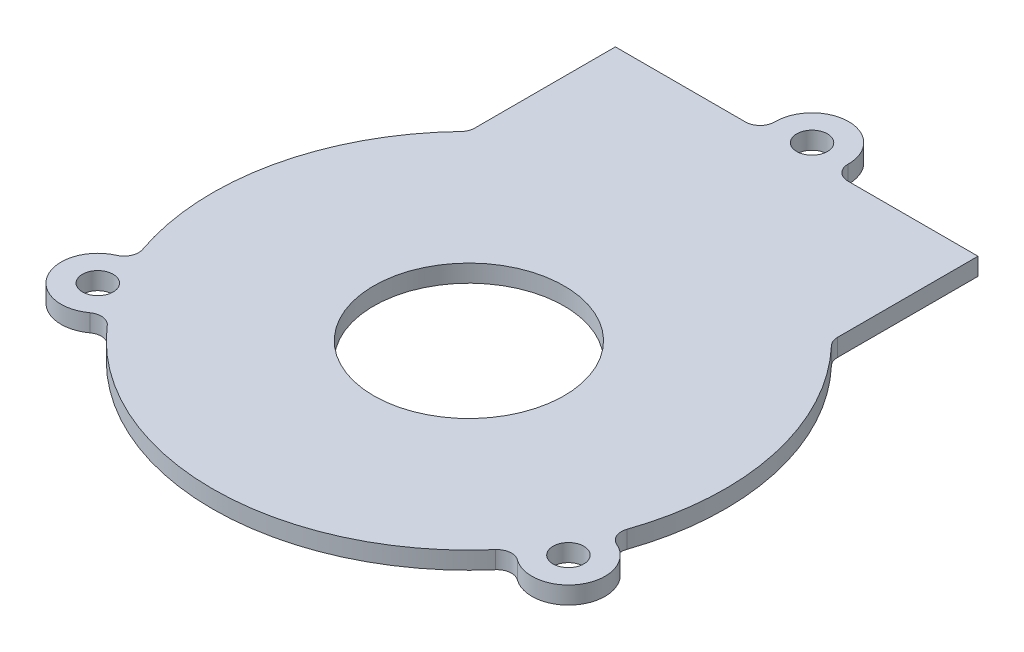
SolidWorks part; units mm, degrees
ref_plane "Front Plane" through (0, 0, 0) normal (0, 0, 1) x (1, 0, 0)
ref_plane "Top Plane" through (0, 0, 0) normal (0, 1, 0) x (1, 0, 0)
ref_plane "Right Plane" through (0, 0, 0) normal (1, 0, 0) x (0, 0, -1)
sketch "Sketch13" plane through (0, 0, 0) normal (0, 1, 0) x (1, 0, 0)
  circle A0 centre (0, 0) radius 35
extrude "Boss-Extrude3" add sketch "Sketch13" along normal blind 2.3813
sketch "Sketch14" plane through (0, 2.3813, 0) normal (0, 1, 0) x (1, 0, 0)
  line L0 (-24.7478, 24.7497) -> (24.7477, 24.7498)
  line L1 (-24.7478, 24.7497) -> (-24.7479, 44.7452)
  line L2 (24.7477, 24.7498) -> (24.7476, 44.7454)
  line L3 (-24.7479, 44.7452) -> (24.7476, 44.7454)
  line L4 (0, 0) -> (60.4611, -34.8658) construction
  line L5 (0, 0) -> (-56.6044, -32.6614) construction
  line L7 (-3.939, 44.1714) -> (-8.8985, 44.1714)
  line L8 (-3.939, 44.1714) -> (-3.939, 47.547)
  line L9 (-3.939, 47.547) -> (-8.8985, 47.547)
  line L10 (-8.8985, 44.1714) -> (-8.8985, 47.547)
  arc A0 (0, 35) -> (-24.7478, 24.7497) centre (0, 0) ccw construction
  circle A1 centre (0, 0) radius 35 construction
  arc A2 (0, 35) -> (-30.3109, -17.4999) centre (0, 0) ccw construction
  arc A3 (0, 35) -> (30.3118, -17.4984) centre (0, 0) ccw
  arc A4 (0, 35) -> (24.7477, 24.7498) centre (0, 0) ccw construction
  circle A5 centre (32.1365, -18.5413) radius 2.1017
  circle A6 centre (32.1365, -18.5413) radius 4.9951
  circle A7 centre (-32.1465, -18.5162) radius 2.0981
  circle A8 centre (-32.1465, -18.5162) radius 4.9995
extrude "Boss-Extrude4" add sketch "Sketch14" against normal up to surface (2.3813 mm away) contours L0 L1 L3 L2 up to face at (0, 0, 35)
sketch "Sketch15" plane through (0, 2.3813, 0) normal (0, 1, 0) x (1, 0, 0)
  line L0 (0, 0) -> (0, 62.3966) construction
  line L1 (-0.0001, 44.7453) -> (0, 46.8414) construction
  line L2 (-24.7479, 44.7452) -> (24.7476, 44.7454) construction
  circle A0 centre (0, 46.8414) radius 2.0961
  circle A1 centre (0, 46.8414) radius 4.996
extrude "Boss-Extrude11" add sketch "Sketch15" against normal up to surface (2.3813 mm away) contours A1 | A0 up to face at (-0.0001, 0, -19.8101)
extrude "Boss-Extrude12" add sketch "Sketch14<6>" against normal up to surface (2.3813 mm away) contours A6 up to face at (0, 0, -29.3038)
sketch "Sketch14<6>" plane through (0, 2.3813, 0) normal (0, 1, 0) x (1, 0, 0) same geometry as "Sketch14"
extrude "Boss-Extrude14" add sketch "Sketch14<8>" against normal up to surface (2.3813 mm away) contours L0 A5 region at (32.1365, 2.3813, 18.5413) up to face at (5.9749, 0, -21.2696)
sketch "Sketch14<8>" plane through (0, 2.3813, 0) normal (0, 1, 0) x (1, 0, 0) same geometry as "Sketch14"
hole_wizard "Ø4.2 (4.2) Diameter Hole1" positions "Sketch22" profile "Sketch23" hole size "Ø4.2" standard "ANSI Metric" end condition through all
sketch "Sketch22" plane through (0, 2.3813, 0) normal (0, 1, 0) x (1, 0, 0)
  point P0 (32.1248, -18.5356)
sketch "Sketch23" plane through (32.1248, 2.3813, 18.5356) normal (1, 0, 0) x (0, 0, 1)
  line L0 (0, 0) -> (0, 2.3812)
  line L1 (0, 2.3812) -> (2.1, 2.3812)
  line L2 (2.1, 2.3812) -> (2.1, 0)
  line L5 (2.1, 0) -> (0, 0)
  line L11 (0, -6.35) -> (0, 107.95) construction
  dimension "Thru Hole Dia." = 4.2
  dimension "Thru Hole Depth" = 2.3813
extrude "Boss-Extrude15" add sketch "Sketch14<11>" against normal up to surface (2.3813 mm away) contours A8 up to face at (32.1248, 0, 20.6356)
sketch "Sketch14<11>" plane through (0, 2.3813, 0) normal (0, 1, 0) x (1, 0, 0) same geometry as "Sketch14"
hole_wizard "Ø4.2 (4.2) Diameter Hole2" positions "Sketch26" profile "Sketch27" hole size "Ø4.2" standard "ANSI Metric" end condition through all
sketch "Sketch26" plane through (0, 2.3813, 0) normal (0, 1, 0) x (1, 0, 0)
  point P0 (-32.148, -18.5088)
  point P2 (-32.148, -18.5088)
sketch "Sketch27" plane through (-32.148, 2.3813, 18.5088) normal (1, 0, 0) x (0, 0, 1)
  line L0 (0, 0) -> (0, 2.3812)
  line L1 (0, 2.3812) -> (2.1, 2.3812)
  line L2 (2.1, 2.3812) -> (2.1, 0)
  line L5 (2.1, 0) -> (0, 0)
  line L11 (0, -6.35) -> (0, 107.95) construction
  dimension "Thru Hole Dia." = 4.2
  dimension "Thru Hole Depth" = 2.3813
fillet "Fillet4" radius 2 1 edges at (-24.7478, 1.1906, -24.7497)
fillet "Fillet6" radius 2 1 edges at (-32.2839, 1.1906, 13.5185)
fillet "Fillet7" radius 2 1 edges at (-27.8924, 1.1906, 21.1427)
fillet "Fillet8" radius 2 1 edges at (27.8812, 1.1906, 21.1574)
fillet "Fillet9" radius 2 1 edges at (32.2715, 1.1906, 13.548)
fillet "Fillet10" radius 2 1 edges at (24.7477, 1.1906, -24.7498)
fillet "Fillet11" radius 2 1 edges at (4.535, 1.1906, -44.7453)
fillet "Fillet12" radius 2 1 edges at (-4.535, 1.1906, -44.7453)
sketch "Sketch28" plane through (0, 2.3813, 0) normal (0, 1, 0) x (1, 0, 0)
  circle A0 centre (0, 0) radius 5
extrude "Cut-Extrude1" cut sketch "Sketch28" against normal up to surface (2.3813 mm away) up to face at (-32.148, 0, 20.6088)
sketch "Sketch29" plane through (0, 2.3813, 0) normal (0, 1, 0) x (1, 0, 0)
  circle A0 centre (0, 0) radius 13
extrude "Cut-Extrude2" cut sketch "Sketch29" against normal up to surface (2.3813 mm away) up to face at (0, 0, 5)
